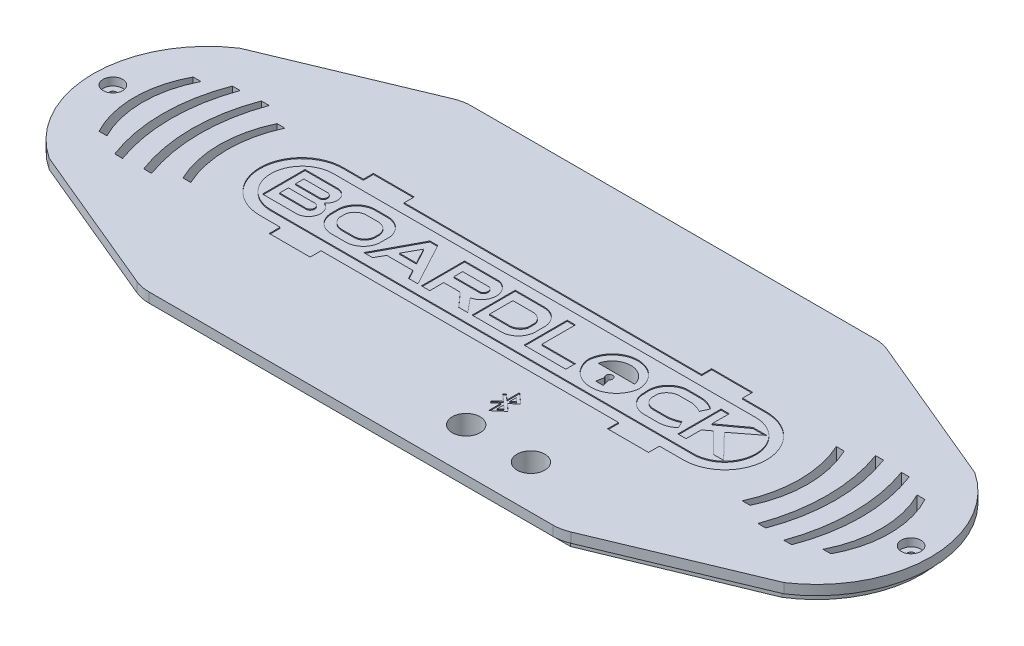
SolidWorks part; units mm, degrees
ref_plane "Front Plane" through (0, 0, 0) normal (0, 0, 1) x (1, 0, 0)
ref_plane "Top Plane" through (0, 0, 0) normal (0, 1, 0) x (1, 0, 0)
ref_plane "Right Plane" through (0, 0, 0) normal (1, 0, 0) x (0, 0, -1)
sketch "Sketch2" plane through (0, 0, 0) normal (0, 1, 0) x (1, 0, 0)
  line L0 (0, 0) -> (102, 0) construction
  line L1 (0, 0) -> (0, -77.2) construction
  line L2 (102, 0) -> (102, -77.2) construction
  line L3 (0, -77.2) -> (102, -77.2) construction
  line L4 (51, 0) -> (51, -77.2) construction
  line L5 (0, -38.6) -> (102, -38.6) construction
  line L6 (-2.5, 2.5) -> (104.5, 2.5)
  line L7 (-2.5, -79.7) -> (104.5, -79.7)
  line L8 (104.5, 2.5) -> (144.7372, -14.2911)
  line L9 (104.5, -79.7) -> (144.7372, -62.9089)
  line L10 (102, -38.6) -> (155.3, -38.6) construction
  line L11 (-2.5, -79.7) -> (-42.7372, -62.9089)
  line L12 (-2.5, 2.5) -> (-42.7372, -14.2911)
  line L13 (0, 0) -> (102, 0)
  line L14 (102, 0) -> (104.5, 0)
  line L15 (104.5, 0) -> (142.7026, -15.7437)
  line L16 (104.5, -77.2) -> (142.7026, -61.4563)
  line L17 (102, -77.2) -> (104.5, -77.2)
  line L18 (-2.5, -77.2) -> (-40.7026, -61.4563)
  line L19 (0, -77.2) -> (-2.5, -77.2)
  line L20 (-2.5, 0) -> (-40.7026, -15.7437)
  line L21 (0, 0) -> (-2.5, 0)
  line L22 (0, -77.2) -> (102, -77.2)
  line L23 (0.5, 0) -> (0.5, -77.2) construction
  line L24 (0, -76.7) -> (97.7329, -76.7) construction
  line L25 (0.5, -74.6) -> (97.3633, -74.6) construction
  line L26 (63.32, -77.2) -> (63.32, 0) construction
  line L27 (0.5, -62.6) -> (97.044, -62.6) construction
  line L28 (75.32, -62.6) -> (75.32, -74.6) construction
  line L29 (79.83, -62.6) -> (79.83, -74.6) construction
  line L30 (91.83, -62.6) -> (91.83, -74.6) construction
  line L31 (69.32, -62.6) -> (69.32, -74.6) construction
  line L32 (63.32, -68.6) -> (75.32, -68.6) construction
  line L33 (85.83, -62.6) -> (85.83, -74.6) construction
  line L34 (79.83, -68.6) -> (91.83, -68.6) construction
  arc A0 (144.7372, -14.2911) -> (144.7372, -62.9089) centre (128.65, -38.6) cw
  arc A1 (-42.7372, -14.2911) -> (-42.7372, -62.9089) centre (-26.65, -38.6) ccw
  arc A2 (142.7026, -15.7437) -> (142.7026, -61.4563) centre (128.65, -38.6) cw
  arc A3 (-40.7026, -15.7437) -> (-40.7026, -61.4563) centre (-26.65, -38.6) ccw
  circle A4 centre (69.32, -68.6) radius 3.55
  circle A5 centre (85.83, -68.6) radius 3.55
  point P16 (157.8, -38.6)
  dimension "D3" = 2.5
  dimension "D10" = 2.5
  dimension "D1" = 77.2
  dimension "D2" = 102
  dimension "D4" = 2.5
  dimension "D5" = 2.5
  dimension "D6" = 2.5
  dimension "D7" = 0.5
  dimension "D8" = 2.5
  dimension "D9" = 53.3
  dimension "D11" = 0.5
  dimension "D12" = 2.1
  dimension "D13" = 62.82
  dimension "D14" = 12
  dimension "D15" = 12
  dimension "D16" = 4.51
  dimension "D17" = 12
  dimension "D18" = 6
  dimension "D19" = 6
  dimension "D20" = 6
  dimension "D21" = 6
extrude "Boss-Extrude3" add sketch "Sketch2" along normal blind 2.5 contours L6 L8 A0 L9 L7 L11 A1 L12
extrude "Boss-Extrude4" add sketch "Sketch2<8>" against normal blind 2.5 contours L20 A3 L18 L19 L22 L17 L16 A2 L15 L14 L13 L21 region at (50.8464, 0, 38.4266)
sketch "Sketch2<8>" plane through (0, 0, 0) normal (0, 1, 0) x (1, 0, 0) same geometry as "Sketch2"
sketch "Sketch3" plane through (0, 2.5, 0) normal (0, 1, 0) x (1, 0, 0)
  line L0 (-55.8, -38.6) -> (157.8, -38.6) construction
  line L1 (51, 2.5) -> (51, -79.7) construction
  line L2 (-2.5, 2.5) -> (104.5, 2.5) construction
  line L3 (-2.5, -79.7) -> (104.5, -79.7) construction
  line L4 (201.4283, 144.6262) -> (1084.095, 144.6262) construction
  line L5 (-2.9873, -27.462) -> (1.9495, -27.462)
  line L6 (1.9495, -27.462) -> (1.9495, -24.9021)
  line L7 (1.9495, -24.9021) -> (12.3717, -24.9021)
  line L8 (12.3717, -24.9021) -> (12.3717, -27.462)
  line L9 (12.3717, -27.462) -> (88.2398, -27.462)
  line L10 (88.2398, -27.462) -> (88.2398, -24.9021)
  line L11 (88.2398, -24.9021) -> (98.6886, -24.9021)
  line L12 (98.6886, -24.9021) -> (98.6886, -27.462)
  line L13 (98.6886, -27.462) -> (104.6245, -27.462)
  line L14 (104.6245, -48.6746) -> (98.6886, -48.6746)
  line L15 (98.6886, -48.6746) -> (98.6886, -51.4646)
  line L16 (98.6886, -51.4646) -> (88.2398, -51.4646)
  line L17 (88.2398, -51.4646) -> (88.2398, -48.6746)
  line L18 (88.2398, -48.6746) -> (12.3717, -48.6746)
  line L19 (12.3717, -48.6746) -> (12.3717, -51.4646)
  line L20 (12.3717, -51.4646) -> (1.9495, -51.4646)
  line L21 (1.9495, -51.4646) -> (1.9495, -48.6746)
  line L22 (1.9495, -48.6746) -> (-2.9873, -48.6746)
  line L23 (-2.9873, -30.0692) -> (104.7002, -30.0692)
  line L24 (104.7002, -46.0158) -> (-3.1948, -46.0158)
  line L25 (-7.6306, -32.7625) -> (-7.6306, -43.6232)
  line L26 (-7.6306, -43.6232) -> (1.1441, -43.6232)
  line L27 (-7.6306, -32.7625) -> (0.7133, -32.7625)
  line L28 (5.3465, -39.2139) -> (5.3465, -36.9174)
  line L29 (-5.6807, -35.0072) -> (0.6, -35.0072)
  line L30 (-5.6807, -35.0072) -> (-5.6807, -37.1385)
  line L31 (-5.6807, -37.1385) -> (0.6, -37.1385)
  line L33 (-5.6807, -38.9524) -> (0.7133, -38.9524)
  line L34 (-5.6807, -38.9524) -> (-5.6807, -41.1744)
  line L35 (-5.6807, -41.1744) -> (0.7133, -41.1744)
  line L41 (10.1371, -35.0072) -> (13.3467, -35.0072)
  line L42 (9.866, -32.6184) -> (13.2281, -32.6184)
  line L43 (18.2229, -43.6232) -> (20.4629, -43.6232)
  line L44 (18.0967, -36.7888) -> (18.0967, -39.563)
  line L45 (16.1379, -37.4286) -> (16.1379, -38.7874)
  line L46 (13.8283, -43.6232) -> (10.2518, -43.6232)
  line L47 (20.4629, -43.6232) -> (21.7662, -41.3167)
  line L48 (13.6087, -41.3167) -> (10.2917, -41.3167)
  line L49 (21.7662, -41.3167) -> (28.4046, -41.3167)
  line L50 (7.3404, -38.9659) -> (7.3404, -37.4286)
  line L51 (28.4046, -41.3167) -> (29.6467, -43.6232)
  line L52 (29.6467, -43.6232) -> (32.0292, -43.6232)
  line L53 (32.0292, -43.6232) -> (26.1026, -32.6184)
  line L54 (26.1026, -32.6184) -> (24.0876, -32.6184)
  line L55 (24.0876, -32.6184) -> (18.2229, -43.6232)
  line L56 (22.9065, -39.2139) -> (27.2439, -39.2139)
  line L57 (27.2439, -39.2139) -> (25.0951, -35.224)
  line L58 (25.0951, -35.224) -> (22.9065, -39.2139)
  line L59 (32.928, -32.6184) -> (32.928, -43.6232)
  line L60 (32.928, -43.6232) -> (35.043, -43.6232)
  line L61 (35.043, -43.6232) -> (35.043, -40.0634)
  line L62 (35.043, -40.0634) -> (39.244, -40.0634)
  line L63 (39.244, -40.0634) -> (42.431, -43.6232)
  line L64 (42.431, -43.6232) -> (44.7378, -43.6232)
  line L65 (44.7378, -43.6232) -> (41.7936, -40.0634)
  line L66 (32.928, -32.6184) -> (41.7936, -32.6184)
  line L67 (35.043, -35.224) -> (35.043, -37.4805)
  line L68 (35.043, -37.4805) -> (41.7936, -37.4805)
  line L69 (35.043, -35.224) -> (41.7936, -35.224)
  line L70 (45.8463, -32.6184) -> (45.8463, -43.6232)
  line L71 (45.8463, -43.6232) -> (52.8329, -43.6232)
  line L72 (45.8463, -32.6184) -> (52.9687, -32.6184)
  line L73 (57.6458, -36.7888) -> (57.6458, -39.563)
  line L74 (47.8647, -35.224) -> (47.8647, -41.1744)
  line L75 (47.8647, -41.1744) -> (52.6, -41.1744)
  line L76 (47.8647, -35.224) -> (52.6, -35.224)
  line L77 (55.6246, -37.1385) -> (55.6246, -39.1866)
  line L78 (59.1096, -32.6184) -> (59.1096, -43.6232)
  line L79 (59.1096, -43.6232) -> (69.7525, -43.6232)
  line L80 (69.7525, -43.6232) -> (69.7525, -41.1876)
  line L81 (69.7525, -41.1876) -> (61.1954, -41.1876)
  line L82 (61.1954, -41.1876) -> (61.1954, -32.6184)
  line L83 (61.1954, -32.6184) -> (59.1096, -32.6184)
  line L84 (72.3273, -37.9056) -> (81.6057, -37.9056)
  line L85 (76.285, -40.2528) -> (75.9572, -42.1923)
  line L86 (75.9572, -42.1923) -> (77.8461, -42.1923)
  line L87 (77.8461, -42.1923) -> (77.3335, -40.2528)
  line L88 (90.3322, -35.0072) -> (93.3549, -35.0072)
  line L89 (96.0824, -35.9398) -> (96.9798, -33.9561)
  line L90 (92.9888, -32.6184) -> (89.5293, -32.6184)
  line L91 (86.9671, -37.333) -> (86.9671, -38.6)
  line L92 (86.9671, -38.6) -> (86.9671, -39.0585)
  line L93 (89.7665, -41.1876) -> (93.2664, -41.1876)
  line L94 (96.1597, -40.3804) -> (97.0399, -42.1923)
  line L95 (93.0498, -43.6232) -> (90.1278, -43.6232)
  line L96 (84.9417, -38.6) -> (84.9417, -39.5139)
  line L97 (98.3461, -32.6195) -> (98.3461, -43.6259)
  line L98 (98.3461, -43.6259) -> (100.4335, -43.6259)
  line L99 (100.4335, -43.6259) -> (100.4335, -39.7387)
  line L100 (100.4335, -39.7387) -> (102.2231, -38.4318)
  line L101 (102.2231, -38.4318) -> (107.3754, -43.6259)
  line L102 (107.3754, -43.6259) -> (110.0073, -43.6259)
  line L103 (110.0073, -43.6259) -> (103.904, -37.333)
  line L104 (103.904, -37.333) -> (110.0073, -32.6195)
  line L105 (110.0073, -32.6195) -> (106.4905, -32.6195)
  line L106 (106.4905, -32.6195) -> (100.4335, -37.0424)
  line L107 (100.4335, -37.0424) -> (100.4335, -32.6195)
  line L108 (100.4335, -32.6195) -> (98.3461, -32.6195)
  arc A0 (86.9671, -37.333) -> (90.3322, -35.0072) centre (90.1278, -38.3088) cw
  arc A1 (93.3549, -35.0072) -> (96.0824, -35.9398) centre (92.5616, -41.7819) cw
  arc A2 (-42.7372, -14.2911) -> (-42.7372, -62.9089) centre (-26.65, -38.6) ccw construction
  arc A3 (144.7372, -62.9089) -> (144.7372, -14.2911) centre (128.65, -38.6) ccw construction
  arc A4 (-2.9873, -27.462) -> (-2.9873, -48.6746) centre (-3.1948, -38.0683) ccw
  arc A5 (104.6245, -27.462) -> (104.6245, -48.6746) centre (104.776, -38.0683) cw
  arc A6 (-2.9873, -30.0692) -> (-3.1948, -46.0158) centre (-3.091, -38.0425) ccw
  arc A7 (104.7002, -30.0692) -> (104.7002, -46.0158) centre (104.7002, -38.0425) cw
  arc A8 (0.7133, -32.7625) -> (2.2325, -37.6827) centre (0.6, -35.492) cw
  arc A9 (1.1441, -43.6232) -> (2.2325, -37.6827) centre (1.0303, -40.5324) ccw
  arc A10 (0.6, -35.0072) -> (0.6, -37.1385) centre (0.3019, -36.0728) cw
  arc A11 (0.7133, -41.1744) -> (0.7133, -38.9524) centre (0.9838, -40.0634) ccw
  arc A12 (5.3465, -36.9174) -> (9.866, -32.6184) centre (10.1371, -37.4286) cw
  arc A13 (18.0967, -36.7888) -> (13.2281, -32.6184) centre (13.2836, -37.4805) ccw
  arc A14 (5.3465, -39.2139) -> (10.2518, -43.6232) centre (10.0037, -38.9659) ccw
  arc A15 (13.8283, -43.6232) -> (18.0967, -39.563) centre (13.6087, -39.1187) ccw
  arc A16 (10.1371, -35.0072) -> (7.3404, -37.4286) centre (10.2483, -37.9613) ccw
  arc A17 (13.3467, -35.0072) -> (16.1379, -37.4286) centre (13.2781, -37.9056) cw
  arc A18 (16.1379, -38.7874) -> (13.6087, -41.3167) centre (13.3904, -38.5692) cw
  arc A19 (10.2917, -41.3167) -> (7.3404, -38.9659) centre (10.2917, -38.2887) cw
  arc A20 (41.7936, -35.224) -> (41.7936, -37.4805) centre (41.488, -36.3523) cw
  arc A21 (41.7936, -40.0634) -> (41.7936, -32.6184) centre (40.9073, -36.3409) ccw
  arc A22 (52.9687, -32.6184) -> (57.6458, -36.7888) centre (53.222, -37.0421) cw
  arc A23 (57.6458, -39.563) -> (52.8329, -43.6232) centre (53.2093, -39.1866) cw
  arc A24 (52.6, -35.224) -> (55.6246, -37.1385) centre (52.8789, -38.1299) cw
  arc A25 (55.6246, -39.1866) -> (52.6, -41.1744) centre (52.8755, -38.2986) cw
  arc A26 (70.3877, -38.6) -> (83.4404, -38.6) centre (76.9141, -38.8997) cw
  arc A27 (70.3877, -38.6) -> (83.4404, -38.6) centre (76.9141, -37.8504) ccw
  arc A28 (76.285, -40.2528) -> (77.3335, -40.2528) centre (76.8092, -39.581) cw
  arc A29 (72.3273, -37.9056) -> (81.6057, -37.9056) centre (76.9665, -38.9919) cw
  arc A30 (96.9798, -33.9561) -> (92.9888, -32.6184) centre (93.0498, -39.0585) ccw
  arc A31 (89.5293, -32.6184) -> (84.9417, -38.6) centre (89.9999, -37.7293) ccw
  arc A32 (86.9671, -39.0585) -> (89.7665, -41.1876) centre (89.6538, -38.4308) ccw
  arc A33 (93.2664, -41.1876) -> (96.1597, -40.3804) centre (92.4973, -32.8415) ccw
  arc A34 (84.9417, -39.5139) -> (90.1278, -43.6232) centre (89.7907, -38.7214) ccw
  arc A35 (93.0498, -43.6232) -> (97.0399, -42.1923) centre (93.1901, -37.7354) ccw
extrude "Logo" cut sketch "Sketch3" against normal blind 0.25 contours L26 A9 A8 L27 L25 A11 L35 L34 L33 L29 A10 L31 L30 | L46 A15 L44 A13 L42 A12 L28 A14 L48 A19 L50 A16 L41 A17 L45 A18 | L54 L55 L43 L47 L49 L51 L52 L53 L58 L57 L56 | L65 A21 L66 L59 L60 L61 L62 L63 L64 L69 A20 L68 L67 | A23 L73 A22 L72 L70 L71 L77 A25 L75 L74 L76 A24 | A26 A27 L85 A28 L87 L86 L84 A29 | L95 A35 L94 A33 L93 A32 L92 L91 A0 L88 A1 L89 A30 L90 A31 L96 A34 | L107 L108 L97 L98 L99 L100 L101 L102 L103 L104 L105 L106 | L82 L83 L78 L79 L80 L81 | A4 L22 L21 L20 L19 L18 L17 L16 L15 L14 A5 L13 L12 L11 L10 L9 L8 L7 L6 L5 | A6 L24 A7 L23 | L78 L79 L80 L81 L82 L83 region at (-2.2321, 2.5, 38.3038) region at (5.5149, 2.5, 38.0657) region at (21.3111, 2.5, 38.2038) region at (37.3608, 2.5, 32.7798) region at (49.4075, 2.5, 32.7799) region at (60.1525, 2.5, 32.7715) region at (88.1536, 2.5, 35.4525) region at (102.8661, 2.5, 37.8921) region at (76.9141, 2.5, 32.5442)
fillet "Fillet1" radius 10 4 edges at (-2.5, 1.25, -2.5) (104.5, 1.25, -2.5) (104.5, 1.25, 79.7) (-2.5, 1.25, 79.7)
sketch "Sketch4" plane through (0, 2.5, 0) normal (0, 1, 0) x (1, 0, 0)
  line L0 (-55.8, -38.6) -> (157.8, -38.6) construction
  line L1 (51, 2.5) -> (51, -79.7) construction
  line L2 (-0.4972, 2.5) -> (102.4972, 2.5) construction
  line L3 (-0.4972, -79.7) -> (102.4972, -79.7) construction
  line L4 (-42.3364, -26.6) -> (-42.3364, -50.6) construction
  line L5 (-40.3364, -26.6) -> (-40.3364, -50.6) construction
  line L6 (-35.3364, -23.6) -> (-35.3364, -53.6) construction
  line L7 (-33.3364, -23.6) -> (-33.3364, -53.6) construction
  line L8 (-28.3364, -23.2) -> (-28.3364, -53.2) construction
  line L9 (-26.3364, -23.2) -> (-26.3364, -53.2) construction
  line L10 (-21.3364, -26.2) -> (-21.3364, -50.2) construction
  line L11 (-19.3364, -26.2) -> (-19.3364, -50.2) construction
  line L12 (-42.3364, -26.6) -> (-40.3364, -26.6)
  line L13 (-42.3364, -50.6) -> (-40.3364, -50.6)
  line L14 (-35.3364, -53.6) -> (-33.3364, -53.6)
  line L15 (-35.3364, -23.6) -> (-33.3364, -23.6)
  line L16 (-28.3364, -23.2) -> (-26.3364, -23.2)
  line L17 (-28.3364, -53.2) -> (-26.3364, -53.2)
  line L18 (-21.3364, -50.2) -> (-19.3364, -50.2)
  line L19 (-21.3364, -26.2) -> (-19.3364, -26.2)
  line L20 (121.3364, -26.2) -> (121.3364, -50.2) construction
  line L21 (123.3364, -26.2) -> (123.3364, -50.2) construction
  line L22 (128.3364, -23.2) -> (128.3364, -53.2) construction
  line L23 (130.3364, -23.2) -> (130.3364, -53.2) construction
  line L24 (135.3364, -23.6) -> (135.3364, -53.6) construction
  line L25 (137.3364, -23.6) -> (137.3364, -53.6) construction
  line L26 (142.3364, -26.6) -> (142.3364, -50.6) construction
  line L27 (144.3364, -26.6) -> (144.3364, -50.6) construction
  line L28 (123.3364, -26.2) -> (121.3364, -26.2)
  line L29 (123.3364, -50.2) -> (121.3364, -50.2)
  line L30 (130.3364, -53.2) -> (128.3364, -53.2)
  line L31 (130.3364, -23.2) -> (128.3364, -23.2)
  line L32 (137.3364, -23.6) -> (135.3364, -23.6)
  line L33 (137.3364, -53.6) -> (135.3364, -53.6)
  line L34 (144.3364, -50.6) -> (142.3364, -50.6)
  line L35 (144.3364, -26.6) -> (142.3364, -26.6)
  arc A0 (-42.7372, -14.2911) -> (-42.7372, -62.9089) centre (-26.65, -38.6) ccw construction
  arc A1 (144.7372, -62.9089) -> (144.7372, -14.2911) centre (128.65, -38.6) ccw construction
  arc A2 (-42.3364, -26.6) -> (-42.3364, -50.6) centre (-19.91, -38.6) ccw
  arc A3 (-40.3364, -26.6) -> (-40.3364, -50.6) centre (-16.7181, -38.6) ccw
  arc A4 (-35.3364, -23.6) -> (-35.3364, -53.6) centre (3.8054, -38.6) ccw
  arc A5 (-33.3364, -53.6) -> (-33.3364, -23.6) centre (8.2465, -38.6) cw
  arc A6 (-28.3364, -23.2) -> (-28.3364, -53.2) centre (11.3609, -38.2) ccw
  arc A7 (-26.3364, -23.2) -> (-26.3364, -53.2) centre (14.8909, -38.2) ccw
  arc A8 (-21.3364, -26.2) -> (-21.3364, -50.2) centre (3.9499, -38.2) ccw
  arc A9 (-19.3364, -26.2) -> (-19.3364, -50.2) centre (6.9686, -38.2) ccw
  arc A10 (121.3364, -26.2) -> (121.3364, -50.2) centre (95.0314, -38.2) cw
  arc A11 (123.3364, -26.2) -> (123.3364, -50.2) centre (98.0501, -38.2) cw
  arc A12 (128.3364, -23.2) -> (128.3364, -53.2) centre (87.1091, -38.2) cw
  arc A13 (130.3364, -23.2) -> (130.3364, -53.2) centre (90.6391, -38.2) cw
  arc A14 (135.3364, -53.6) -> (135.3364, -23.6) centre (93.7535, -38.6) ccw
  arc A15 (137.3364, -23.6) -> (137.3364, -53.6) centre (98.1946, -38.6) cw
  arc A16 (142.3364, -26.6) -> (142.3364, -50.6) centre (118.7181, -38.6) cw
  arc A17 (144.3364, -26.6) -> (144.3364, -50.6) centre (121.91, -38.6) cw
  dimension "D1" = 24
  dimension "D2" = 12
  dimension "D3" = 30
  dimension "D4" = 15
  dimension "D5" = 2
  dimension "D6" = 2
  dimension "D7" = 2
  dimension "D8" = 2
  dimension "D9" = 7
  dimension "D10" = 7
  dimension "D11" = 7
extrude "SoundGaps" cut sketch "Sketch4" against normal up to next
sketch "Sketch5" plane through (0, 2.5, 0) normal (0, 1, 0) x (1, 0, 0)
  circle A2 centre (69.32, -68.6) radius 3.55
  circle A3 centre (85.83, -68.6) radius 3.55
  dimension "D1" = 7.1
extrude "Buttons" cut sketch "Sketch5" against normal up to next
extrude "Cut-Extrude5" cut sketch "Sketch3<5>" against normal up to next contours A29 L84 | L85 L86 L87 A28 region at (76.9665, 2.5, 36.3712)
sketch "Sketch3<5>" plane through (0, 2.5, 0) normal (0, 1, 0) x (1, 0, 0) same geometry as "Sketch3"
sketch "Sketch9" plane through (0, 2.5, 0) normal (0, 1, 0) x (1, 0, 0)
  line L0 (-55.8, -38.6) -> (157.8, -38.6) construction
  arc A0 (-42.7372, -14.2911) -> (-42.7372, -62.9089) centre (-26.65, -38.6) ccw construction
  arc A1 (144.7372, -62.9089) -> (144.7372, -14.2911) centre (128.65, -38.6) ccw construction
  circle A2 centre (-50.8, -38.6) radius 2.5
  circle A3 centre (-50.8, -38.6) radius 0.9
  circle A4 centre (152.8, -38.6) radius 2.5
  circle A5 centre (152.8, -38.6) radius 0.9
  dimension "D2" = 5
  dimension "D1" = 5
extrude "Cut-Extrude6" cut sketch "Sketch9" against normal blind 2 contours A4 | A2
extrude "Cut-Extrude7" cut sketch "Sketch9<4>" against normal up to next contours A5 | A3
sketch "Sketch9<4>" plane through (0, 2.5, 0) normal (0, 1, 0) x (1, 0, 0) same geometry as "Sketch9"
sketch "Sketch10" plane through (0, 2.5, 0) normal (0, 1, 0) x (1, 0, 0)
  line L0 (69.32, -68.6) -> (69.32, -48.6746) construction
  line L1 (88.2398, -48.6746) -> (12.3717, -48.6746) construction
  line L2 (115.6352, -94.9025) -> (318.3019, -94.9025) construction
  line L3 (69.82, -51.182) -> (69.82, -64.7502) construction
  line L42 (69.0237, -62.6526) -> (69.0435, -59.4185)
  line L43 (69.0435, -59.4185) -> (67.6195, -60.6789)
  line L44 (67.6195, -60.6789) -> (67.1687, -60.1696)
  line L45 (67.1687, -60.1696) -> (68.8931, -58.6551)
  line L46 (68.8931, -58.6551) -> (67.1368, -57.1201)
  line L47 (67.1368, -57.1201) -> (67.6195, -56.6695)
  line L48 (67.6195, -56.6695) -> (69.0283, -57.9008)
  line L49 (69.0283, -57.9008) -> (69.0283, -54.6775)
  line L50 (69.0283, -54.6775) -> (71.6999, -57.0673)
  line L51 (71.6999, -57.0673) -> (69.8872, -58.6718)
  line L52 (69.8872, -58.6718) -> (71.715, -60.3068)
  line L53 (71.715, -60.3068) -> (69.0237, -62.6526)
  line L60 (69.7231, -56.2295) -> (69.7231, -57.9008)
  line L61 (69.7231, -57.9008) -> (70.6676, -57.0651)
  line L62 (70.6676, -57.0651) -> (69.7231, -56.2295)
  line L63 (69.7231, -59.4527) -> (69.7231, -61.1309)
  line L64 (69.7231, -61.1309) -> (70.6676, -60.2953)
  line L65 (70.6676, -60.2953) -> (69.7231, -59.4527)
  dimension "D2" = 0.5
extrude "Cut-Extrude8" cut sketch "Sketch10" against normal blind 0.25
